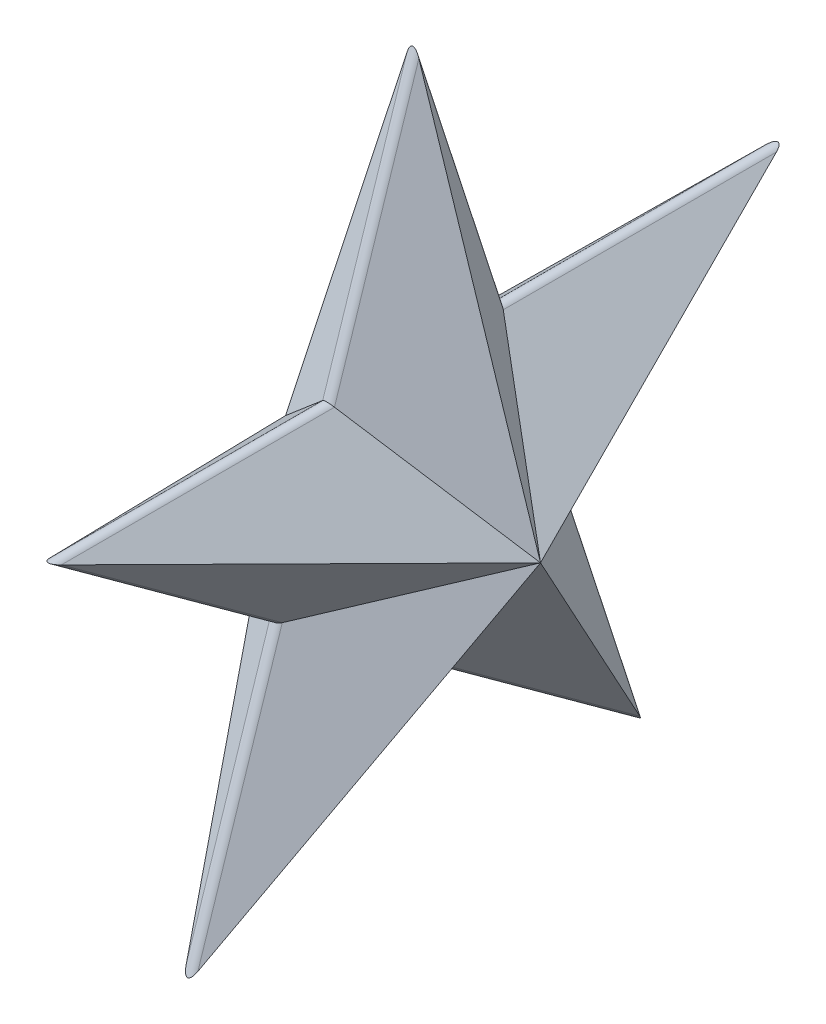
SolidWorks part; units mm, degrees
ref_plane "Front Plane" through (0, 0, 0) normal (0, 0, 1) x (1, 0, 0)
ref_plane "Top Plane" through (0, 0, 0) normal (0, 1, 0) x (1, 0, 0)
ref_plane "Right Plane" through (0, 0, 0) normal (1, 0, 0) x (0, 0, -1)
sketch "Sketch1" plane through (0, 0, 0) normal (0, 1, 0) x (1, 0, 0)
  circle A0 centre (0, 0) radius 9.525
sketch "Sketch3" plane through (0, 0, 0) normal (1, 0, 0) x (0, 0, -1)
  line L6 (0, 21.2985) -> (2.6433, 13.1632)
  line L7 (11.1973, 13.1632) -> (2.6433, 13.1632)
  line L8 (0, 21.2985) -> (-2.6433, 13.1632)
  line L9 (6.9203, 0) -> (0, 5.0279)
  line L10 (11.1973, 13.1632) -> (4.277, 8.1353)
  line L12 (-2.6433, 13.1632) -> (-11.1973, 13.1632)
  line L13 (4.277, 8.1353) -> (6.9203, 0)
  line L14 (0, 5.0279) -> (-6.9203, 0)
  line L15 (-4.277, 8.1353) -> (-11.1973, 13.1632)
  line L16 (-4.277, 8.1353) -> (-6.9203, 0)
  circle A2 centre (0, 9.525) radius 11.7735 construction
ref_plane "Plane1" through (3.81, 0, 0) normal (1, 0, 0) x (0, 0, -1)
sketch "Sketch5" plane through (3.81, 0, 0) normal (1, 0, 0) x (0, 0, -1)
  point P0 (0, 9.525)
loft "Loft4" add profiles "Sketch3", "Sketch5"
ref_plane "Plane4" through (-3.81, 0, 0) normal (1, 0, 0) x (0, 0, -1)
sketch "Sketch8" plane through (-3.81, 0, 0) normal (1, 0, 0) x (0, 0, -1)
  point P0 (0, 9.525)
loft "Loft5" add profiles "Sketch8", "Sketch3<3>"
sketch "Sketch3<3>" plane through (0, 0, 0) normal (1, 0, 0) x (0, 0, -1) same geometry as "Sketch3"
fillet "Fillet1" radius 0.254 2 edges
fillet "Fillet2" radius 0.254 8 edges
